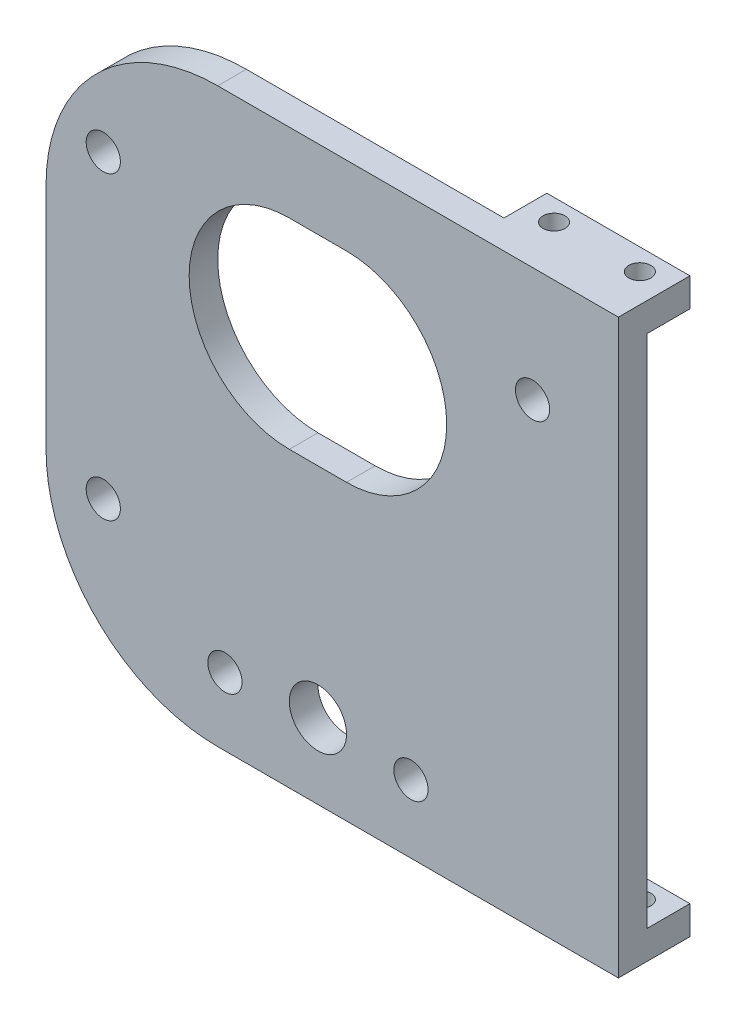
SolidWorks part; units mm, degrees
material "Polycarbonate"
ref_plane "Front Plane" through (0, 0, 0) normal (0, 0, 1) x (1, 0, 0)
ref_plane "Top Plane" through (0, 0, 0) normal (0, 1, 0) x (1, 0, 0)
ref_plane "Right Plane" through (0, 0, 0) normal (1, 0, 0) x (0, 0, -1)
sketch "Sketch1" plane through (0, 0, 0) normal (0, 0, 1) x (1, 0, 0)
  line L1 (-31.75, 31.75) -> (31.75, 31.75)
  line L2 (-31.75, 31.75) -> (-31.75, -31.75)
  line L3 (-31.75, -31.75) -> (31.75, -31.75)
  line L4 (31.75, 31.75) -> (31.75, -31.75)
  line L5 (-31.75, 31.75) -> (31.75, -31.75) construction
  line L6 (-31.75, -31.75) -> (31.75, 31.75) construction
  point P0 (0, 0)
  dimension "D1" = 63.5
  dimension "D2" = 63.5
extrude "Boss-Extrude1" add sketch "Sketch1" along normal blind 3.175
sketch "Sketch2" plane through (0, 0, 0) normal (0, 0, -1) x (-1, 0, 0)
  line L0 (31.75, -31.75) -> (-31.75, -31.75) construction
  line L1 (-25.4, -31.75) -> (-15.875, -31.75)
  line L3 (-25.4, -28.575) -> (-15.875, -28.575)
  line L4 (-15.875, -31.75) -> (-15.875, -28.575)
  line L5 (-31.75, -31.75) -> (-31.75, 31.75) construction
  line L7 (-31.75, -31.75) -> (-25.4, -31.75)
  line L8 (-31.75, -31.75) -> (-31.75, -28.575)
  line L9 (-31.75, -28.575) -> (-25.4, -28.575)
  dimension "D1" = 3.175
  dimension "D2" = 15.875
  dimension "D4" = 6.35
extrude "Boss-Extrude2" add sketch "Sketch2" along normal blind 4.7625
hole_wizard "#2 Clearance Hole1" positions "Sketch3" profile "Sketch4" hole size "#2" standard "ANSI Inch" end condition up to next
sketch "Sketch3" plane through (0, -28.575, 0) normal (0, 1, 0) x (1, 0, 0)
  line L0 (15.875, 4.7625) -> (15.875, 0) construction
  line L6 (31.75, 4.7625) -> (31.75, 0) construction
  point P0 (28.575, 2.3813)
  point P5 (15.875, 2.3813)
  point P21 (19.05, 2.3813)
  dimension "D1" = 3.175
  dimension "D2" = 3.175
sketch "Sketch4" plane through (28.575, -28.575, -2.3813) normal (1, 0, 0) x (0, 0, 1)
  line L0 (0, 0) -> (0, 3.175)
  line L1 (0, 3.175) -> (1.2192, 3.175)
  line L2 (1.2192, 3.175) -> (1.2192, 0)
  line L5 (1.2192, 0) -> (0, 0)
  line L11 (0, -6.35) -> (0, 107.95) construction
  dimension "Thru Hole Dia." = 2.4384
  dimension "Thru Hole Depth" = 3.175
fillet "Fillet1" radius 19.05 2 edges at (-31.75, -31.75, 1.5875) (-31.75, 31.75, 1.5875)
sketch "Sketch5" plane through (0, 0, 0) normal (0, 0, -1) x (-1, 0, 0)
  line L0 (-15.875, -31.75) -> (-15.875, -28.575) construction
  line L1 (-31.75, 31.75) -> (-15.875, 31.75)
  line L2 (-31.75, 31.75) -> (-31.75, 28.575)
  line L3 (-31.75, 28.575) -> (-15.875, 28.575)
  line L4 (-15.875, 31.75) -> (-15.875, 28.575)
  dimension "D1" = 3.175
extrude "Boss-Extrude3" add sketch "Sketch5" along normal blind 4.7625
hole_wizard "#2 Clearance Hole2" positions "Sketch6" profile "Sketch7" hole size "#2" standard "ANSI Inch" end condition up to next
sketch "Sketch6" plane through (0, 28.575, 0) normal (0, -1, 0) x (-1, 0, 0)
  point P0 (-19.05, 2.3813)
  point P3 (-28.575, 2.3813)
sketch "Sketch7" plane through (19.05, 28.575, -2.3813) normal (1, 0, 0) x (0, 0, -1)
  line L0 (0, 0) -> (0, 3.175)
  line L1 (0, 3.175) -> (1.2192, 3.175)
  line L2 (1.2192, 3.175) -> (1.2192, 0)
  line L5 (1.2192, 0) -> (0, 0)
  line L11 (0, -6.35) -> (0, 107.95) construction
  dimension "Thru Hole Dia." = 2.4384
  dimension "Thru Hole Depth" = 3.175
sketch "Sketch8" plane through (0, 0, 3.175) normal (0, 0, 1) x (1, 0, 0)
  line L0 (-25.4, 19.05) -> (-25.4, -14.2875) construction
  line L1 (-25.4, -14.2875) -> (-11.9062, -24.2094) construction
  line L2 (-11.9062, -24.2094) -> (8.7313, -24.2094) construction
  line L3 (8.7313, -24.2094) -> (22.225, -24.2094) construction
  line L4 (22.225, -24.2094) -> (22.225, 19.05) construction
  line L5 (22.225, 19.05) -> (-25.4, 19.05) construction
  line L6 (-12.7, -31.75) -> (31.75, -31.75) construction
  line L7 (31.75, -31.75) -> (31.75, 31.75) construction
  circle A0 centre (-25.4, 19.05) radius 3.175
  circle A1 centre (-25.4, -14.2875) radius 3.175
  circle A2 centre (22.225, 19.05) radius 3.175
  circle A3 centre (8.7313, -24.2094) radius 3.175
  circle A4 centre (-11.9062, -24.2094) radius 3.175
  dimension "D8" = 6.35
  dimension "D1" = 33.3375
  dimension "D2" = 47.625
  dimension "D3" = 43.2594
  dimension "D4" = 13.4937
  dimension "D5" = 20.6375
  dimension "D6" = 7.5406
  dimension "D7" = 9.525
extrude "Boss-Extrude4" add sketch "Sketch8" against normal blind 3.175 from surface starting at face at (3.0209, 0, 0)
hole_wizard "#6 Clearance Hole1" positions "Sketch9" profile "Sketch10" hole size "#6" standard "ANSI Inch" end condition through all
sketch "Sketch9" plane through (0, 0, -3.175) normal (0, 0, -1) x (-1, 0, 0)
  point P0 (-22.225, 19.05)
  point P3 (25.4, 19.05)
  point P6 (25.4, -14.2875)
  point P9 (11.9062, -24.2094)
  point P12 (-8.7313, -24.2094)
sketch "Sketch10" plane through (22.225, 19.05, -3.175) normal (1, 0, 0) x (0, 1, 0)
  line L0 (0, 0) -> (0, 6.35)
  line L1 (0, 6.35) -> (1.8986, 6.35)
  line L2 (1.8986, 6.35) -> (1.8986, 0)
  line L5 (1.8986, 0) -> (0, 0)
  line L11 (0, -6.35) -> (0, 107.95) construction
  dimension "Thru Hole Dia." = 3.7973
  dimension "Thru Hole Depth" = 6.35
sketch "Sketch11" plane through (0, 0, 3.175) normal (0, 0, 1) x (1, 0, 0)
  line L0 (-25.4, 19.05) -> (22.225, 19.05) construction
  line L1 (-15.875, 23.0188) -> (12.7, 23.0188) construction
  line L2 (-15.875, 23.0188) -> (-15.875, 0.7938) construction
  line L3 (-15.875, 0.7938) -> (12.7, 0.7938) construction
  line L4 (12.7, 23.0188) -> (12.7, 0.7938) construction
  line L5 (31.75, 31.75) -> (-12.7, 31.75) construction
  line L6 (-4.7625, 11.9063) -> (1.5875, 11.9063) construction
  line L7 (-4.7625, 23.0188) -> (1.5875, 23.0188)
  line L8 (-4.7625, 0.7938) -> (1.5875, 0.7938)
  circle A0 centre (22.225, 19.05) radius 1.8986 construction
  circle A1 centre (-25.4, 19.05) radius 1.8986 construction
  circle A2 centre (22.225, 19.05) radius 1.8986 construction
  circle A3 centre (-25.4, 19.05) radius 1.8986 construction
  arc A5 (-4.7625, 23.0188) -> (-4.7625, 0.7938) centre (-4.7625, 11.9063) ccw
  arc A6 (1.5875, 0.7938) -> (1.5875, 23.0188) centre (1.5875, 11.9063) ccw
  circle A7 centre (-1.5875, -23.4156) radius 3.175
  circle A8 centre (8.7313, -24.2094) radius 1.8986 construction
  circle A9 centre (-11.9062, -24.2094) radius 1.8986 construction
  circle A10 centre (8.7313, -24.2094) radius 1.8986 construction
  circle A11 centre (-11.9062, -24.2094) radius 1.8986 construction
  point P10 (-1.5875, 19.05)
  point P11 (-1.5875, 23.0188)
  point P17 (-1.5875, 11.9063)
  point P19 (-15.875, 11.9063)
  point P27 (-1.5875, 23.0188)
  point P28 (-1.5875, 0.7938)
  dimension "D5" = 6.35
  dimension "D1" = 28.575
  dimension "D2" = 22.225
  dimension "D3" = 8.7312
  dimension "D4" = 0.7937
extrude "Cut-Extrude1" cut sketch "Sketch11" against normal up to next
